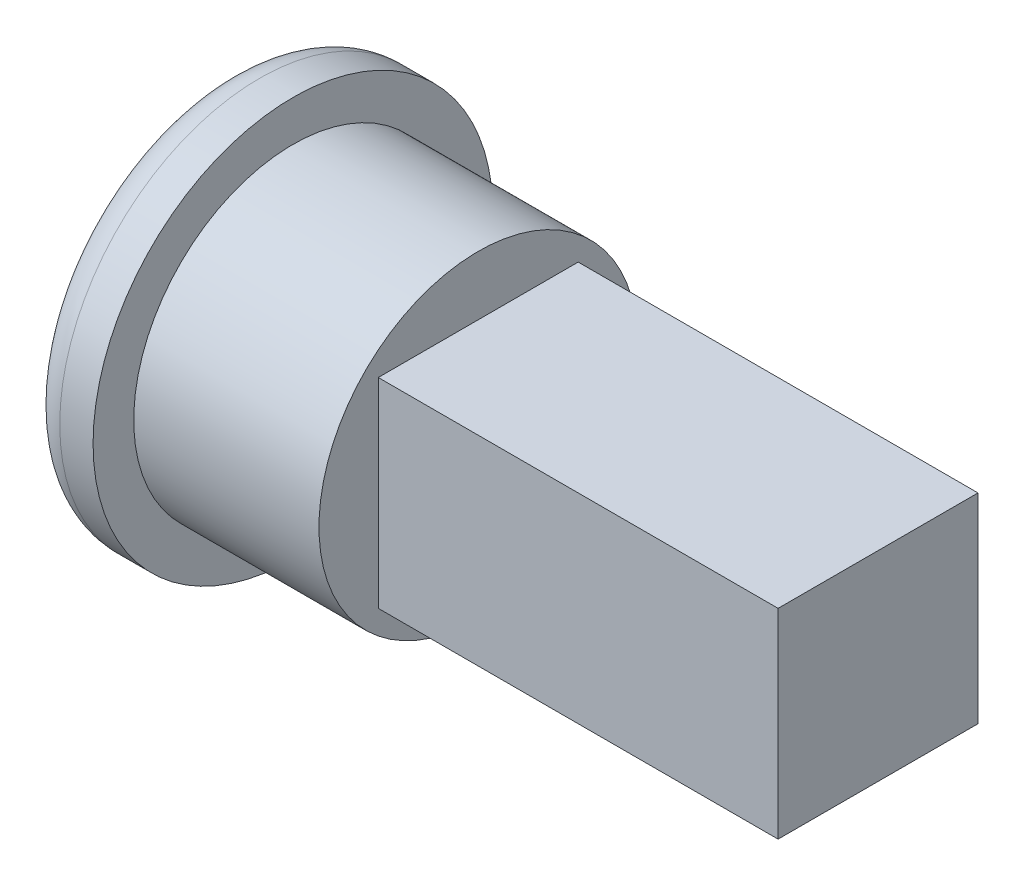
SolidWorks part; units mm, degrees
ref_plane "Front Plane" through (0, 0, 0) normal (0, 0, 1) x (1, 0, 0)
ref_plane "Top Plane" through (0, 0, 0) normal (0, 1, 0) x (1, 0, 0)
ref_plane "Right Plane" through (0, 0, 0) normal (1, 0, 0) x (0, 0, -1)
sketch "Sketch1" plane through (0, 0, 0) normal (1, 0, 0) x (0, 0, -1)
  circle A0 centre (0, 0) radius 4.78
  dimension "D1" = 9.56
extrude "Boss-Extrude1" add sketch "Sketch1" along normal mid plane 5.56
sketch "Sketch2" plane through (2.78, 0, 0) normal (1, 0, 0) x (0, 0, -1)
  line L1 (-3, 3) -> (3, 3)
  line L2 (-3, 3) -> (-3, -3)
  line L3 (-3, -3) -> (3, -3)
  line L4 (3, 3) -> (3, -3)
  line L5 (-3, 3) -> (3, -3) construction
  line L6 (-3, -3) -> (3, 3) construction
  point P0 (0, 0)
  dimension "D1" = 6
extrude "Boss-Extrude2" add sketch "Sketch2" along normal blind 12
sketch "Sketch3" plane through (-2.78, 0, 0) normal (-1, 0, 0) x (0, 0, 1)
  circle A0 centre (0, 0) radius 6
  dimension "D1" = 12
extrude "Boss-Extrude3" add sketch "Sketch3" along normal blind 2
fillet "Fillet1" radius 1 1 edges at (-4.78, 0, 6)
